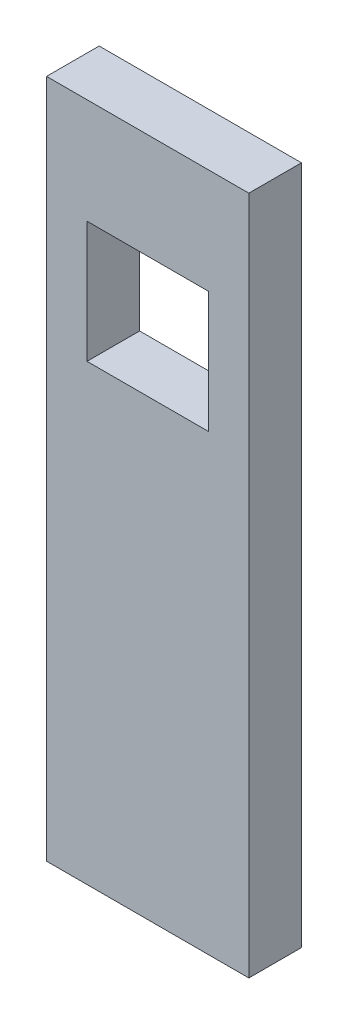
SolidWorks part; units mm, degrees
ref_plane "Front Plane" through (0, 0, 0) normal (0, 0, 1) x (1, 0, 0)
ref_plane "Top Plane" through (0, 0, 0) normal (0, 1, 0) x (1, 0, 0)
ref_plane "Right Plane" through (0, 0, 0) normal (1, 0, 0) x (0, 0, -1)
sketch "Sketch1" plane through (0, 0, 0) normal (0, 0, 1) x (1, 0, 0)
  line L0 (0, 67.2) -> (0, 44.8)
  line L1 (0, 67.2) -> (20, 67.2)
  line L2 (0, 44.8) -> (0, 39.6)
  line L3 (20, 0) -> (0, 0)
  line L4 (4, 56.8) -> (16, 56.8)
  line L5 (4, 44.8) -> (16, 44.8)
  line L6 (4, 56.8) -> (4, 44.8)
  line L7 (16, 56.8) -> (16, 44.8)
  line L8 (0, 44.8) -> (20, 44.8) construction
  line L9 (0, 39.6) -> (20, 39.6) construction
  line L10 (0, 39.6) -> (0, 27.6)
  line L11 (0, 27.6) -> (0, 22.4)
  line L12 (20, 44.8) -> (20, 39.6)
  line L13 (20, 67.2) -> (20, 44.8)
  line L14 (0, 22.4) -> (0, 0)
  line L15 (20, 39.6) -> (20, 27.6)
  line L16 (20, 27.6) -> (20, 22.4)
  line L17 (20, 22.4) -> (20, 0)
  line L18 (0, 27.6) -> (20, 27.6) construction
  line L19 (20, 22.4) -> (0, 22.4) construction
  line L20 (10, -0.0005) -> (10, 4.0956) construction
  point P18 (10, 44.8)
  point P20 (10, 56.8)
  point P21 (10, 67.2)
  dimension "D1" = 22.4
  dimension "D2" = 12
  dimension "D3" = 5.2
  dimension "D4" = 20
  dimension "D5" = 12
  dimension "D6" = 12
extrude "Boss-Extrude1" add sketch "Sketch1" along normal mid plane 5.2
